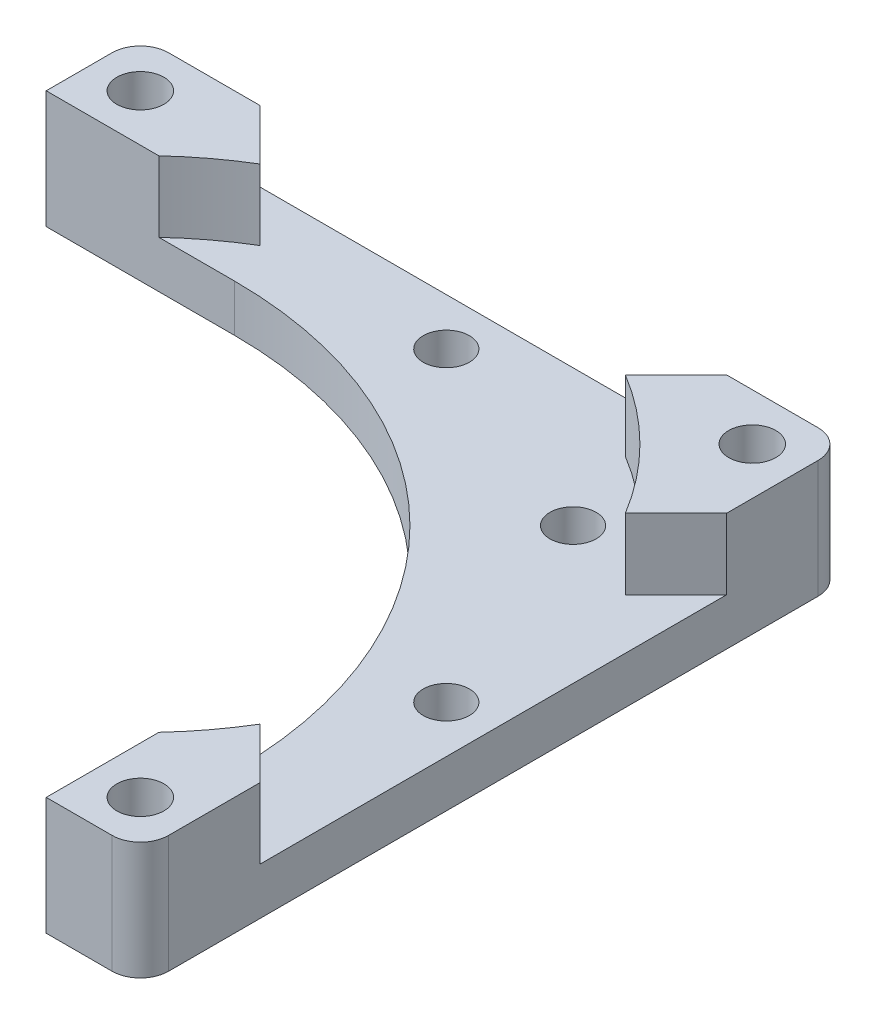
SolidWorks part; units mm, degrees
ref_plane "Front Plane" through (0, 0, 0) normal (0, 0, 1) x (1, 0, 0)
ref_plane "Top Plane" through (0, 0, 0) normal (0, 1, 0) x (1, 0, 0)
ref_plane "Right Plane" through (0, 0, 0) normal (1, 0, 0) x (0, 0, -1)
sketch "Sketch1" plane through (0, 0, 0) normal (0, 1, 0) x (1, 0, 0)
  line L1 (-95.25, -95.25) -> (95.25, -95.25)
  line L2 (-95.25, -95.25) -> (-95.25, 95.25)
  line L3 (-95.25, 95.25) -> (95.25, 95.25)
  line L4 (95.25, -95.25) -> (95.25, 95.25)
  line L5 (-95.25, -95.25) -> (95.25, 95.25) construction
  line L6 (-95.25, 95.25) -> (95.25, -95.25) construction
  point P0 (0, 0)
  dimension "D1" = 190.5
  dimension "D2" = 190.5
extrude "Boss-Extrude1" add sketch "Sketch1" along normal blind 12.7
fillet "Fillet1" radius 7.62 4 edges at (-95.25, 6.35, 95.25) (95.25, 6.35, 95.25) (95.25, 6.35, -95.25) (-95.25, 6.35, -95.25)
ref_plane "Plane1" through (12.7, 0, 0) normal (1, 0, 0) x (0, 0, -1)
sketch "Sketch6" plane through (0, 12.7, 0) normal (0, 1, 0) x (1, 0, 0)
  line L0 (-95.25, 87.63) -> (-95.25, -87.63) construction
  line L1 (-82.55, -82.55) -> (82.55, -82.55)
  line L2 (-82.55, -82.55) -> (-82.55, 82.55)
  line L3 (-82.55, 82.55) -> (82.55, 82.55)
  line L4 (82.55, -82.55) -> (82.55, 82.55)
  line L5 (-82.55, -82.55) -> (82.55, 82.55) construction
  line L6 (-82.55, 82.55) -> (82.55, -82.55) construction
  line L7 (-87.63, -95.25) -> (87.63, -95.25) construction
  point P0 (0, 0)
  dimension "D1" = 12.7
  dimension "D2" = 12.7
sketch "Sketch7" plane through (0, 12.7, 0) normal (0, 1, 0) x (1, 0, 0)
  line L0 (95.25, 95.25) -> (-95.25, -95.25) construction
  line L1 (62.9211, 95.25) -> (49.2652, 81.5941)
  line L2 (81.5941, 49.2652) -> (95.25, 62.9211)
  line L8 (95.25, -87.63) -> (95.25, 87.63)
  line L9 (87.63, 95.25) -> (-87.63, 95.25)
  line L14 (-95.25, 87.63) -> (-95.25, -87.63)
  line L15 (-87.63, -95.25) -> (87.63, -95.25)
  line L16 (95.25, -87.63) -> (95.25, 87.63)
  line L17 (87.63, 95.25) -> (-87.63, 95.25)
  line L22 (-95.25, 87.63) -> (-95.25, -87.63)
  line L23 (-87.63, -95.25) -> (87.63, -95.25)
  circle A0 centre (0, 0) radius 95.3135
  arc A5 (95.25, 87.63) -> (87.63, 95.25) centre (87.63, 87.63) ccw
  arc A6 (-87.63, 95.25) -> (-95.25, 87.63) centre (-87.63, 87.63) ccw
  arc A7 (-95.25, -87.63) -> (-87.63, -95.25) centre (-87.63, -87.63) ccw
  arc A8 (87.63, -95.25) -> (95.25, -87.63) centre (87.63, -87.63) ccw
  arc A9 (95.25, 87.63) -> (87.63, 95.25) centre (87.63, 87.63) ccw
  arc A10 (-87.63, 95.25) -> (-95.25, 87.63) centre (-87.63, 87.63) ccw
  arc A11 (-95.25, -87.63) -> (-87.63, -95.25) centre (-87.63, -87.63) ccw
  arc A12 (87.63, -95.25) -> (95.25, -87.63) centre (87.63, -87.63) ccw
  line M17 (95.25, -87.63) -> (95.25, 87.63)
  arc M18 (95.25, 87.63) -> (87.63, 95.25) centre (87.63, 87.63) ccw
  line M19 (87.63, 95.25) -> (-87.63, 95.25)
  dimension "D3" = 190.627
  dimension "D2" = 190.5
  dimension "D4" = 45
  dimension "D5" = 7.62
  dimension "D6" = 7.62
  dimension "D7" = 22.86
  dimension "D8" = 22.86
  dimension "D1" = 0
extrude "Boss-Extrude3" add sketch "Sketch7" along normal blind 19.05 contours L0 A9 L1 A0 M19 | L0 A0 L2 M18 M17 region at (84.5318, 12.7, -70.1242) region at (70.1242, 12.7, -84.5318)
ref_axis "Axis1" through (0, 195.7992, 0) along (0, -1, 0)
pattern_circular "CirPattern1" count 4 over 360 about axis through (0, 195.7992, 0) along (0, -1, 0) of "Boss-Extrude3"
sketch "Sketch8" plane through (0, 12.7, 0) normal (0, 1, 0) x (1, 0, 0)
  circle A0 centre (0, 0) radius 82.55
  circle A1 centre (0, 82.55) radius 6.223
  circle A2 centre (58.3717, 58.3717) radius 6.223
  circle A3 centre (82.55, 0) radius 6.223
  circle A4 centre (58.3717, -58.3717) radius 6.223
  circle A5 centre (0, -82.55) radius 6.223
  circle A6 centre (-58.3717, -58.3717) radius 6.223
  circle A7 centre (-82.55, 0) radius 6.223
  circle A8 centre (-58.3717, 58.3717) radius 6.223
  point P21 (0, 0)
  dimension "D1" = 165.1
  dimension "D2" = 12.446
  dimension "D3" = 8
extrude "Cut-Extrude2" cut sketch "Sketch8" against normal blind 25.4 contours A1 | A8 | A7 | A6 | A5 | A4 | A3 | A2
sketch "Sketch10" plane through (0, 12.7, 0) normal (0, 1, 0) x (1, 0, 0)
  line L1 (-95.25, 62.9211) -> (-95.25, -62.9211) construction
  line L3 (-95.25, 38.1) -> (38.1, 38.1)
  line L5 (-95.25, 38.1) -> (-95.25, -95.25)
  line L7 (-95.25, -95.25) -> (38.1, -95.25)
  line L8 (38.1, 38.1) -> (38.1, -95.25)
  line L9 (-62.9211, -95.25) -> (62.9211, -95.25) construction
  line L10 (62.9211, 95.25) -> (-62.9211, 95.25) construction
  line L11 (95.25, -62.9211) -> (95.25, 62.9211) construction
  line L13 (-95.25, -95.25) -> (-38.1, -95.25)
  line L14 (-95.25, -95.25) -> (-95.25, -38.1)
  line L15 (-95.25, -38.1) -> (-38.1, -38.1)
  line L16 (-38.1, -95.25) -> (-38.1, -38.1)
  line L17 (-95.25, -95.25) -> (95.25, -95.25)
  line L18 (-95.25, -95.25) -> (-95.25, 95.25)
  line L19 (-95.25, 95.25) -> (95.25, 95.25)
  line L20 (95.25, -95.25) -> (95.25, 95.25)
  circle M7 centre (-82.55, 0) radius 6.223
  circle M8 centre (-58.3717, -58.3717) radius 6.223
  circle M9 centre (0, -82.55) radius 6.223
  line M16 (-95.25, 62.9211) -> (-95.25, -62.9211)
  line M17 (-95.25, -62.9211) -> (-81.5941, -49.2652)
  arc M18 (-81.5941, -49.2652) -> (-49.2652, -81.5941) centre (0, 0) ccw
  line M19 (-49.2652, -81.5941) -> (-62.9211, -95.25)
  line M20 (-62.9211, -95.25) -> (62.9211, -95.25)
  dimension "D2" = 57.15
  dimension "D1" = 57.15
  dimension "D3" = 57.15
  dimension "D4" = 57.15
extrude "Cut-Extrude3" cut sketch "Sketch10" against normal through all both and the other way through all contours L16 L7 L8 L3 L15 M16 M9 M7 | L16 L15 L5 M20 M17 M18 M19 M8 | L14 L13 L16 L15 region at (-19.6398, 12.7, 19.6398) region at (-66.675, 12.7, 38.9082)
fillet "Fillet2" radius 12.7 3 edges at (38.1, 6.35, 95.25) (38.1, 6.35, -38.1) (-95.25, 6.35, -38.1)
sketch "Sketch11" plane through (0, 31.75, 0) normal (0, 1, 0) x (1, 0, 0)
  line L0 (95.25, 62.9211) -> (95.25, 87.63) construction
  line L1 (87.63, 95.25) -> (62.9211, 95.25) construction
  circle A0 centre (82.55, 82.55) radius 6.35
  circle A1 centre (82.55, 82.55) radius 3.2385
  dimension "D3" = 12.7
  dimension "D4" = 6.477
  dimension "D1" = 12.7
  dimension "D2" = 12.7
extrude "Cut-Extrude4" cut sketch "Sketch11" against normal up to surface (19.05 mm away) contours A0 up to face at (58.3717, 12.7, -52.1487)
extrude "Cut-Extrude5" cut sketch "Sketch11<3>" against normal through all contours A1 region at (82.55, 31.75, -82.55)
sketch "Sketch11<3>" plane through (0, 31.75, 0) normal (0, 1, 0) x (1, 0, 0) same geometry as "Sketch11"
pattern_circular "CirPattern2" count 4 over 360 about axis through (0, 195.7992, 0) along (0, -1, 0) of "Cut-Extrude5", "Cut-Extrude4"
sketch "Sketch12" plane through (0, 12.7, 0) normal (0, 1, 0) x (1, 0, 0)
  line L0 (50.8, -95.25) -> (62.9211, -95.25) construction
  line L1 (-95.25, -95.25) -> (69.85, -95.25)
  line L2 (-95.25, -95.25) -> (-95.25, 69.85)
  line L3 (-95.25, 69.85) -> (-44.45, 69.85)
  line L4 (69.85, -95.25) -> (69.85, -44.45)
  line L5 (-95.25, 87.63) -> (-95.25, 62.9211) construction
  line L6 (95.25, -62.9211) -> (95.25, 62.9211) construction
  line L7 (62.9211, 95.25) -> (-62.9211, 95.25) construction
  line L11 (69.85, -44.45) -> (-44.45, -44.45)
  line L12 (-44.45, 69.85) -> (-44.45, -44.45)
  dimension "D1" = 25.4
  dimension "D2" = 25.4
  dimension "D3" = 114.3
extrude "Cut-Extrude6" cut sketch "Sketch12" against normal through all both and the other way through all
sketch "Sketch13" plane through (0, 12.7, 0) normal (0, 1, 0) x (1, 0, 0)
  line L2 (-44.45, 69.85) -> (-44.45, -44.45)
  line L3 (-44.45, -44.45) -> (69.85, -44.45)
  line L4 (-95.25, 87.63) -> (-95.25, 69.85) construction
  line L5 (69.85, -95.25) -> (87.63, -95.25) construction
  arc A0 (-44.45, 69.85) -> (69.85, -44.45) centre (-44.45, -44.45) cw
  dimension "D1" = 114.3
  dimension "D2" = 50.8
  dimension "D3" = 50.8
extrude "Cut-Extrude7" cut sketch "Sketch13" against normal through all both and the other way through all
